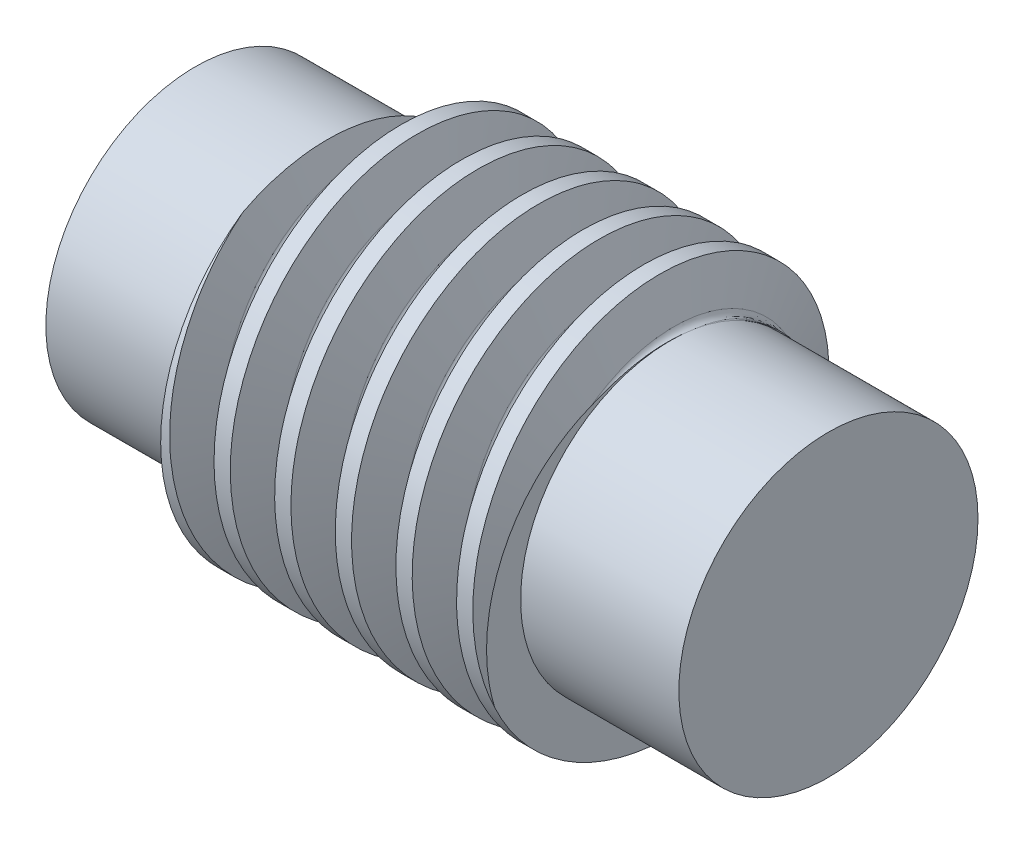
SolidWorks part; units mm, degrees
note: '?' marks a value the reader was unsure of.
ref_plane "前视基准面" through (0, 0, 0) normal (0, 0, 1) x (1, 0, 0)
ref_plane "上视基准面" through (0, 0, 0) normal (0, 1, 0) x (1, 0, 0)
ref_plane "右视基准面" through (0, 0, 0) normal (1, 0, 0) x (0, 0, -1)
ref_axis "基准轴1" through (-10.9638, 0, 0) along (1, 0, 0)?
sketch "草图1" plane through (0, 0, 0) normal (0, 0, 1) x (1, 0, 0)
  line L0 (-56.8494, 0) -> (118.6822, 0) construction
  line L1 (0, 48.1623) -> (0, -71.9241) construction
  line L2 (0, 10) -> (0, 0)
  line L3 (-10.9638, 0) -> (40.5935, 0) construction
  line L7 (0, 10) -> (16.4, 10)
  line L13 (0, 0) -> (16.4, 0)
  line L14 (16.4, 0) -> (16.4, 10)
  dimension "da1" = 10
  dimension "B1" = 16.4
revolve "旋转1" add sketch "草图1" angle 360 about L0
sketch "草图2" plane through (0, 0, 0) normal (1, 0, 0) x (0, 0, -1)
  circle A0 centre (0, 0) radius 9
  dimension "d1" = 18
sketch "草图3" plane through (0, 0, 0) normal (0, 0, 1) x (1, 0, 0)
  line L0 (0, 25.9401) -> (0, 0) construction
  line L1 (-3.4481, 10) -> (-1.1494, 10)
  line L2 (0, 10) -> (16.4, 10) construction
  line L3 (-1.1494, 10) -> (-1.8773, 8)
  line L4 (-2.2344, 7.75) -> (-2.3631, 7.75)
  line L5 (-2.2987, 10) -> (-2.2987, 7.75) construction
  line L6 (0, 0) -> (8.7963, 0) construction
  line L7 (-3.0841, 9) -> (-1.5133, 9) construction
  line L8 (-2.7202, 8) -> (-3.4481, 10)
  line L9 (-3.4481, 10) -> (-3.4481, -10) construction
  line L10 (-2.2987, 10) -> (0, 10) construction
  arc A0 (-2.7202, 8) -> (-2.3631, 7.75) centre (-2.3631, 8.13) ccw
  arc A1 (-2.2344, 7.75) -> (-1.8773, 8) centre (-2.2344, 8.13) ccw
  point P14 (-2.6292, 7.75)
  point P19 (-1.9683, 7.75)
  dimension "ppn" = 0.38
  dimension "df1" = 15.5
  dimension "d1" = 18
  dimension "0.5px" = 1.5708
  dimension "aa1" = 20
  dimension "aa" = 20
sketch "草图4" plane through (0, 0, 0) normal (1, 0, 0) x (0, 0, -1)
  circle A0 centre (0, 0) radius 7.75
sketch "草图5" plane through (16.4, 0, 0) normal (1, 0, 0) x (0, 0, -1)
  circle A0 centre (0, 0) radius 7.75 construction
  circle A1 centre (0, 0) radius 7.75
curve "螺旋线/涡状线1" pitch 3.1416 height 32.8 turns 10.4406
sweep "切除-扫描1" cut profiles "草图3" path "螺旋线/涡状线1"
extrude "凸台-拉伸1" add sketch "草图4" against normal blind 8.2
extrude "凸台-拉伸2" add sketch "草图5" along normal blind 8.2
